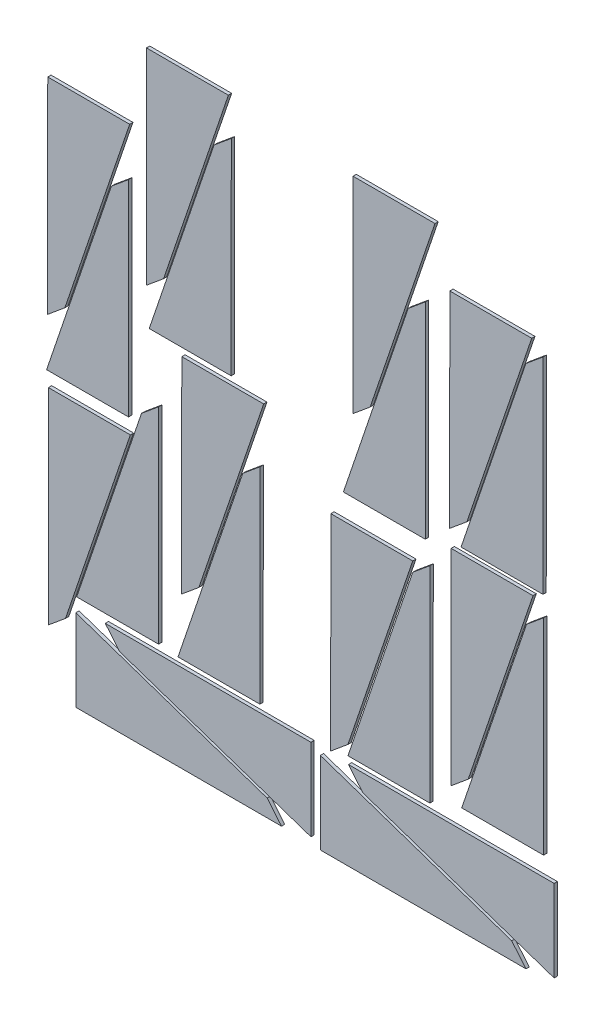
SolidWorks part; units mm, degrees
ref_plane "Front Plane" through (0, 0, 0) normal (0, 0, 1) x (1, 0, 0)
ref_plane "Top Plane" through (0, 0, 0) normal (0, 1, 0) x (1, 0, 0)
ref_plane "Right Plane" through (0, 0, 0) normal (1, 0, 0) x (0, 0, -1)
sketch "Model" plane through (0, 0, 0) normal (0, 0, 1) x (1, 0, 0)
  line L0 (81.73, 0) -> (81.73, 95)
  line L1 (77.73, 99) -> (4, 99)
  line L2 (0, 95) -> (0, 0)
  line L3 (0, 0) -> (9.25, 0)
  line L4 (10.55, -1.3) -> (10.55, -3)
  line L5 (10.55, -3) -> (34.415, -3)
  line L6 (47.315, -3) -> (71.18, -3)
  line L7 (71.18, -3) -> (71.18, -1.3)
  line L8 (72.48, 0) -> (81.73, 0)
  line L9 (35.715, 0) -> (46.015, 0)
  line L10 (34.415, -1.3) -> (34.415, -3)
  line L11 (47.315, -1.3) -> (47.315, -3)
  line L12 (0, 4) -> (9, 4)
  line L13 (9, 4) -> (9, 0)
  line L14 (81.73, 4) -> (72.73, 4)
  line L15 (72.73, 4) -> (72.73, 0)
  line L16 (34.4, 71.8) -> (32.6, 71.8)
  line L17 (32.6, 71.8) -> (32.6, 69)
  line L18 (32.6, 69) -> (34.4, 69)
  line L19 (34.4, 69) -> (34.4, 71.8)
  line L20 (32.5, 71.6) -> (32.5, 71.2)
  line L21 (32.5, 71.2) -> (32.4, 71.2)
  line L22 (32.4, 71.2) -> (32.4, 71.6)
  line L23 (32.4, 71.6) -> (32.5, 71.6)
  line L24 (14.7, 87.6) -> (14.7, 89.4)
  line L25 (14.7, 89.4) -> (11.9, 89.4)
  line L26 (11.9, 89.4) -> (11.9, 87.6)
  line L27 (11.9, 87.6) -> (14.7, 87.6)
  line L28 (14.5, 89.5) -> (14.1, 89.5)
  line L29 (14.1, 89.5) -> (14.1, 89.6)
  line L30 (14.1, 89.6) -> (14.5, 89.6)
  line L31 (14.5, 89.6) -> (14.5, 89.5)
  line L32 (20.8, 48.7) -> (22.6, 48.7)
  line L33 (22.6, 48.7) -> (22.6, 51.5)
  line L34 (22.6, 51.5) -> (20.8, 51.5)
  line L35 (20.8, 51.5) -> (20.8, 48.7)
  line L36 (22.7, 48.9) -> (22.7, 49.3)
  line L37 (22.7, 49.3) -> (22.8, 49.3)
  line L38 (22.8, 49.3) -> (22.8, 48.9)
  line L39 (22.8, 48.9) -> (22.7, 48.9)
  line L40 (5.4, 10.5) -> (3.6, 10.5)
  line L41 (3.6, 10.5) -> (3.6, 7.7)
  line L42 (3.6, 7.7) -> (5.4, 7.7)
  line L43 (5.4, 7.7) -> (5.4, 10.5)
  line L44 (3.5, 10.3) -> (3.5, 9.9)
  line L45 (3.5, 9.9) -> (3.4, 9.9)
  line L46 (3.4, 9.9) -> (3.4, 10.3)
  line L47 (3.4, 10.3) -> (3.5, 10.3)
  line L48 (20.1, 1.8) -> (20.1, 3.6)
  line L49 (20.1, 3.6) -> (17.3, 3.6)
  line L50 (17.3, 3.6) -> (17.3, 1.8)
  line L51 (17.3, 1.8) -> (20.1, 1.8)
  line L52 (19.9, 3.7) -> (19.5, 3.7)
  line L53 (19.5, 3.7) -> (19.5, 3.8)
  line L54 (19.5, 3.8) -> (19.9, 3.8)
  line L55 (19.9, 3.8) -> (19.9, 3.7)
  line L56 (65.5, 94.7) -> (63.7, 94.7)
  line L57 (63.7, 94.7) -> (63.7, 91.9)
  line L58 (63.7, 91.9) -> (65.5, 91.9)
  line L59 (65.5, 91.9) -> (65.5, 94.7)
  line L60 (63.6, 94.5) -> (63.6, 94.1)
  line L61 (63.6, 94.1) -> (63.5, 94.1)
  line L62 (63.5, 94.1) -> (63.5, 94.5)
  line L63 (63.5, 94.5) -> (63.6, 94.5)
  line L64 (61.8, 77.4) -> (63.6, 77.4)
  line L65 (63.6, 77.4) -> (63.6, 80.2)
  line L66 (63.6, 80.2) -> (61.8, 80.2)
  line L67 (61.8, 80.2) -> (61.8, 77.4)
  line L68 (63.7, 77.6) -> (63.7, 78)
  line L69 (63.7, 78) -> (63.8, 78)
  line L70 (63.8, 78) -> (63.8, 77.6)
  line L71 (63.8, 77.6) -> (63.7, 77.6)
  line L72 (62.1, 44.3) -> (63.9, 44.3)
  line L73 (63.9, 44.3) -> (63.9, 47.1)
  line L74 (63.9, 47.1) -> (62.1, 47.1)
  line L75 (62.1, 47.1) -> (62.1, 44.3)
  line L76 (64, 44.5) -> (64, 44.9)
  line L77 (64, 44.9) -> (64.1, 44.9)
  line L78 (64.1, 44.9) -> (64.1, 44.5)
  line L79 (64.1, 44.5) -> (64, 44.5)
  line L80 (43.3, 37.5) -> (45.1, 37.5)
  line L81 (45.1, 37.5) -> (45.1, 40.3)
  line L82 (45.1, 40.3) -> (43.3, 40.3)
  line L83 (43.3, 40.3) -> (43.3, 37.5)
  line L84 (45.2, 37.7) -> (45.2, 38.1)
  line L85 (45.2, 38.1) -> (45.3, 38.1)
  line L86 (45.3, 38.1) -> (45.3, 37.7)
  line L87 (45.3, 37.7) -> (45.2, 37.7)
  line L88 (57.3, 2) -> (57.3, 3.8)
  line L89 (57.3, 3.8) -> (54.5, 3.8)
  line L90 (54.5, 3.8) -> (54.5, 2)
  line L91 (54.5, 2) -> (57.3, 2)
  line L92 (57.1, 3.9) -> (56.7, 3.9)
  line L93 (56.7, 3.9) -> (56.7, 4)
  line L94 (56.7, 4) -> (57.1, 4)
  line L95 (57.1, 4) -> (57.1, 3.9)
  line L96 (38.3, 58.7) -> (40.1, 58.7)
  line L97 (40.1, 58.7) -> (40.1, 61.5)
  line L98 (40.1, 61.5) -> (38.3, 61.5)
  line L99 (38.3, 61.5) -> (38.3, 58.7)
  line L100 (40.2, 58.9) -> (40.2, 59.3)
  line L101 (40.2, 59.3) -> (40.3, 59.3)
  line L102 (40.3, 59.3) -> (40.3, 58.9)
  line L103 (40.3, 58.9) -> (40.2, 58.9)
  line L104 (41.8, 58.7) -> (43.6, 58.7)
  line L105 (43.6, 58.7) -> (43.6, 61.5)
  line L106 (43.6, 61.5) -> (41.8, 61.5)
  line L107 (41.8, 61.5) -> (41.8, 58.7)
  line L108 (43.7, 58.9) -> (43.7, 59.3)
  line L109 (43.7, 59.3) -> (43.8, 59.3)
  line L110 (43.8, 59.3) -> (43.8, 58.9)
  line L111 (43.8, 58.9) -> (43.7, 58.9)
  line L112 (18.0727, 97.8187) -> (18.0543, 66.371)
  line L113 (18.0543, 66.371) -> (20.6886, 68.5619)
  line L114 (20.6886, 68.5619) -> (30.6039, 97.834)
  line L115 (30.6039, 97.834) -> (18.0811, 97.8343)
  line L116 (16.3763, 95.3169) -> (17.1559, 95.3169)
  line L117 (31.0273, 60.8813) -> (31.0457, 92.329)
  line L118 (31.0457, 92.329) -> (28.4114, 90.1381)
  line L119 (28.4114, 90.1381) -> (18.4961, 60.866)
  line L120 (18.4961, 60.866) -> (31.0189, 60.8657)
  line L121 (31.6559, 63.3841) -> (32.4355, 63.3841)
  line L122 (2.9727, 86.4187) -> (2.9543, 54.971)
  line L123 (2.9543, 54.971) -> (5.5886, 57.1619)
  line L124 (5.5886, 57.1619) -> (15.5039, 86.434)
  line L125 (15.5039, 86.434) -> (2.9811, 86.4343)
  line L126 (1.2763, 83.9169) -> (2.0559, 83.9169)
  line L127 (15.3273, 47.5813) -> (15.3457, 79.029)
  line L128 (15.3457, 79.029) -> (12.7114, 76.8381)
  line L129 (12.7114, 76.8381) -> (2.7961, 47.566)
  line L130 (2.7961, 47.566) -> (15.3189, 47.5657)
  line L131 (15.9559, 50.0841) -> (16.7355, 50.0841)
  line L132 (23.4727, 59.6187) -> (23.4543, 28.171)
  line L133 (23.4543, 28.171) -> (26.0886, 30.3619)
  line L134 (26.0886, 30.3619) -> (36.0039, 59.634)
  line L135 (36.0039, 59.634) -> (23.4811, 59.6343)
  line L136 (21.7763, 57.1169) -> (22.5559, 57.1169)
  line L137 (35.4273, 19.5813) -> (35.4457, 51.029)
  line L138 (35.4457, 51.029) -> (32.8114, 48.8381)
  line L139 (32.8114, 48.8381) -> (22.8961, 19.566)
  line L140 (22.8961, 19.566) -> (35.4189, 19.5657)
  line L141 (36.0559, 22.0841) -> (36.8355, 22.0841)
  line L142 (19.9273, 19.7813) -> (19.9457, 51.229)
  line L143 (19.9457, 51.229) -> (17.3114, 49.0381)
  line L144 (17.3114, 49.0381) -> (7.3961, 19.766)
  line L145 (7.3961, 19.766) -> (19.9189, 19.7657)
  line L146 (20.5559, 22.2841) -> (21.3355, 22.2841)
  line L147 (3.0727, 45.3187) -> (3.0543, 13.871)
  line L148 (3.0543, 13.871) -> (5.6886, 16.0619)
  line L149 (5.6886, 16.0619) -> (15.6039, 45.334)
  line L150 (15.6039, 45.334) -> (3.0811, 45.3343)
  line L151 (1.3763, 42.8169) -> (2.1559, 42.8169)
  line L152 (43.2187, 18.4273) -> (11.771, 18.4457)
  line L153 (11.771, 18.4457) -> (13.9619, 15.8114)
  line L154 (13.9619, 15.8114) -> (43.234, 5.8961)
  line L155 (43.234, 5.8961) -> (43.2343, 18.4189)
  line L156 (40.7159, 19.0559) -> (40.7159, 19.8355)
  line L157 (7.2813, 5.0727) -> (38.729, 5.0543)
  line L158 (38.729, 5.0543) -> (36.5381, 7.6886)
  line L159 (36.5381, 7.6886) -> (7.266, 17.6039)
  line L160 (7.266, 17.6039) -> (7.2657, 5.0811)
  line L161 (9.7831, 3.3763) -> (9.7831, 4.1559)
  line L162 (49.6727, 96.6187) -> (49.6543, 65.171)
  line L163 (49.6543, 65.171) -> (52.2886, 67.3619)
  line L164 (52.2886, 67.3619) -> (62.2039, 96.634)
  line L165 (62.2039, 96.634) -> (49.6811, 96.6343)
  line L166 (47.9763, 94.1169) -> (48.7559, 94.1169)
  line L167 (60.7273, 54.0813) -> (60.7457, 85.529)
  line L168 (60.7457, 85.529) -> (58.1114, 83.3381)
  line L169 (58.1114, 83.3381) -> (48.1961, 54.066)
  line L170 (48.1961, 54.066) -> (60.7189, 54.0657)
  line L171 (61.3559, 56.5841) -> (62.1355, 56.5841)
  line L172 (64.4727, 88.8187) -> (64.4543, 57.371)
  line L173 (64.4543, 57.371) -> (67.0886, 59.5619)
  line L174 (67.0886, 59.5619) -> (77.0039, 88.834)
  line L175 (77.0039, 88.834) -> (64.4811, 88.8343)
  line L176 (62.7763, 86.3169) -> (63.5559, 86.3169)
  line L177 (78.7273, 55.7813) -> (78.7457, 87.229)
  line L178 (78.7457, 87.229) -> (76.1114, 85.0381)
  line L179 (76.1114, 85.0381) -> (66.1961, 55.766)
  line L180 (66.1961, 55.766) -> (78.7189, 55.7657)
  line L181 (79.3559, 58.2841) -> (80.1355, 58.2841)
  line L182 (64.6727, 54.8187) -> (64.6543, 23.371)
  line L183 (64.6543, 23.371) -> (67.2886, 25.5619)
  line L184 (67.2886, 25.5619) -> (77.2039, 54.834)
  line L185 (77.2039, 54.834) -> (64.6811, 54.8343)
  line L186 (62.9763, 52.3169) -> (63.7559, 52.3169)
  line L187 (78.8273, 21.2813) -> (78.8457, 52.729)
  line L188 (78.8457, 52.729) -> (76.2114, 50.5381)
  line L189 (76.2114, 50.5381) -> (66.2961, 21.266)
  line L190 (66.2961, 21.266) -> (78.8189, 21.2657)
  line L191 (79.4559, 23.7841) -> (80.2355, 23.7841)
  line L192 (61.4273, 19.4813) -> (61.4457, 50.929)
  line L193 (61.4457, 50.929) -> (58.8114, 48.7381)
  line L194 (58.8114, 48.7381) -> (48.8961, 19.466)
  line L195 (48.8961, 19.466) -> (61.4189, 19.4657)
  line L196 (62.0559, 21.9841) -> (62.8355, 21.9841)
  line L197 (46.2727, 50.2187) -> (46.2543, 18.771)
  line L198 (46.2543, 18.771) -> (48.8886, 20.9619)
  line L199 (48.8886, 20.9619) -> (58.8039, 50.234)
  line L200 (58.8039, 50.234) -> (46.2811, 50.2343)
  line L201 (44.5763, 47.7169) -> (45.3559, 47.7169)
  line L202 (80.4187, 18.3273) -> (48.971, 18.3457)
  line L203 (48.971, 18.3457) -> (51.1619, 15.7114)
  line L204 (51.1619, 15.7114) -> (80.434, 5.7961)
  line L205 (80.434, 5.7961) -> (80.4343, 18.3189)
  line L206 (77.9159, 18.9559) -> (77.9159, 19.7355)
  line L207 (44.6813, 4.8727) -> (76.129, 4.8543)
  line L208 (76.129, 4.8543) -> (73.9381, 7.4886)
  line L209 (73.9381, 7.4886) -> (44.666, 17.4039)
  line L210 (44.666, 17.4039) -> (44.6657, 4.8811)
  line L211 (47.1831, 3.1763) -> (47.1831, 3.9559)
  line L212 (2.9727, 86.4187) -> (2.9727, 86.4343)
  line L213 (2.9727, 86.4343) -> (2.9811, 86.4343)
  line L214 (15.3273, 47.5813) -> (15.3273, 47.5657)
  line L215 (15.3273, 47.5657) -> (15.3189, 47.5657)
  line L216 (18.0727, 97.8187) -> (18.0727, 97.8343)
  line L217 (18.0727, 97.8343) -> (18.0811, 97.8343)
  line L218 (31.0273, 60.8813) -> (31.0273, 60.8657)
  line L219 (31.0273, 60.8657) -> (31.0189, 60.8657)
  line L220 (23.4727, 59.6187) -> (23.4727, 59.6343)
  line L221 (23.4727, 59.6343) -> (23.4811, 59.6343)
  line L222 (35.4273, 19.5813) -> (35.4273, 19.5657)
  line L223 (35.4273, 19.5657) -> (35.4189, 19.5657)
  line L224 (3.0727, 45.3187) -> (3.0727, 45.3343)
  line L225 (3.0727, 45.3343) -> (3.0811, 45.3343)
  line L226 (19.9273, 19.7813) -> (19.9273, 19.7654)
  line L227 (19.9273, 19.7654) -> (19.9189, 19.7657)
  line L228 (7.2657, 5.0811) -> (7.2657, 5.0727)
  line L229 (7.2657, 5.0727) -> (7.2813, 5.0727)
  line L230 (43.2187, 18.4273) -> (43.2343, 18.4273)
  line L231 (43.2343, 18.4273) -> (43.2343, 18.4189)
  line L232 (43.2343, 18.4189) -> (43.2344, 18.4188)
  line L233 (44.6657, 4.8811) -> (44.6657, 4.8727)
  line L234 (44.6657, 4.8727) -> (44.6813, 4.8727)
  line L235 (44.6813, 4.8727) -> (44.6811, 4.8729)
  line L236 (80.4187, 18.3273) -> (80.4343, 18.3273)
  line L237 (80.4343, 18.3273) -> (80.4343, 18.3189)
  line L238 (78.8273, 21.2813) -> (78.8273, 21.2657)
  line L239 (78.8273, 21.2657) -> (78.8189, 21.2657)
  line L240 (64.6727, 54.8187) -> (64.6727, 54.8343)
  line L241 (64.6727, 54.8343) -> (64.6811, 54.8343)
  line L242 (64.6811, 54.8343) -> (64.6808, 54.8344)
  line L243 (61.4273, 19.4813) -> (61.4273, 19.4657)
  line L244 (61.4273, 19.4657) -> (61.4189, 19.4657)
  line L245 (46.2727, 50.2187) -> (46.2727, 50.2343)
  line L246 (46.2727, 50.2343) -> (46.2811, 50.2343)
  line L247 (60.7273, 54.0813) -> (60.7273, 54.0657)
  line L248 (60.7273, 54.0657) -> (60.7189, 54.0657)
  line L249 (49.6727, 96.6187) -> (49.6727, 96.6343)
  line L250 (49.6727, 96.6343) -> (49.6811, 96.6343)
  line L251 (64.4727, 88.8187) -> (64.4727, 88.8343)
  line L252 (64.4727, 88.8343) -> (64.4811, 88.8343)
  line L253 (78.7273, 55.7813) -> (78.7273, 55.7657)
  line L254 (78.7273, 55.7657) -> (78.7189, 55.7657)
  arc A0 (81.73, 95) -> (77.73, 99) centre (77.73, 95) ccw
  arc A1 (4, 99) -> (0, 95) centre (4, 95) ccw
  arc A2 (10.55, -1.3) -> (9.25, 0) centre (9.25, -1.3) ccw
  arc A3 (35.715, 0) -> (34.415, -1.3) centre (35.715, -1.3) ccw
  arc A4 (47.315, -1.3) -> (46.015, 0) centre (46.015, -1.3) ccw
  arc A5 (72.48, 0) -> (71.18, -1.3) centre (72.48, -1.3) ccw
  circle A6 centre (5, 94) radius 1.6
  circle A7 centre (76.73, 94) radius 1.6
  arc A8 (9, 3.8984) -> (9, 4.1016) centre (9, 4) ccw
  arc A9 (0, 4.1016) -> (0, 3.8984) centre (0, 4) ccw
  arc A10 (8.8984, 0) -> (9.1016, 0) centre (9, 0) ccw
  arc A11 (9.1016, 4) -> (8.8984, 4) centre (9, 4) ccw
  arc A12 (72.73, 4.1016) -> (72.73, 3.8984) centre (72.73, 4) ccw
  arc A13 (81.73, 3.8984) -> (81.73, 4.1016) centre (81.73, 4) ccw
  arc A14 (72.6284, 0) -> (72.8316, 0) centre (72.73, 0) ccw
  arc A15 (72.8316, 4) -> (72.6284, 4) centre (72.73, 4) ccw
  circle A16 centre (5, 94) radius 3
  circle A17 centre (76.73, 94) radius 3
  arc A18 (32.6, 71.8317) -> (32.6, 71.7682) centre (32.6, 71.7999) ccw
  arc A19 (34.4, 71.7682) -> (34.4, 71.8317) centre (34.4, 71.7999) ccw
  arc A20 (32.5682, 69) -> (32.6318, 69) centre (32.6, 69) ccw
  arc A21 (32.6318, 71.8) -> (32.5682, 71.8) centre (32.6, 71.8) ccw
  arc A22 (34.4, 68.9682) -> (34.4, 69.0318) centre (34.4, 69) ccw
  arc A23 (32.6, 69.0318) -> (32.6, 68.9682) centre (32.6, 69) ccw
  arc A24 (34.4318, 71.8) -> (34.3682, 71.8) centre (34.4, 71.8) ccw
  arc A25 (34.3682, 69) -> (34.4318, 69) centre (34.4, 69) ccw
  arc A26 (32.4682, 71.2) -> (32.5318, 71.2) centre (32.5, 71.2) ccw
  arc A27 (32.5318, 71.6) -> (32.4682, 71.6) centre (32.5, 71.6) ccw
  arc A28 (32.4, 71.2318) -> (32.4, 71.1683) centre (32.4, 71.2001) ccw
  arc A29 (32.5, 71.1683) -> (32.5, 71.2318) centre (32.5, 71.2001) ccw
  arc A30 (32.4318, 71.6) -> (32.3682, 71.6) centre (32.4, 71.6) ccw
  arc A31 (32.3682, 71.2) -> (32.4318, 71.2) centre (32.4, 71.2) ccw
  arc A32 (32.5, 71.5683) -> (32.5, 71.6318) centre (32.5, 71.6) ccw
  arc A33 (32.4, 71.6318) -> (32.4, 71.5683) centre (32.4, 71.6) ccw
  arc A34 (14.7318, 89.4) -> (14.6683, 89.4) centre (14.7, 89.4) ccw
  arc A35 (14.6683, 87.6) -> (14.7318, 87.6) centre (14.7, 87.6) ccw
  arc A36 (11.9, 89.4318) -> (11.9, 89.3683) centre (11.9, 89.4001) ccw
  arc A37 (14.7, 89.3683) -> (14.7, 89.4318) centre (14.7, 89.4001) ccw
  arc A38 (11.8682, 87.6) -> (11.9318, 87.6) centre (11.9, 87.6) ccw
  arc A39 (11.9318, 89.4) -> (11.8682, 89.4) centre (11.9, 89.4) ccw
  arc A40 (14.7, 87.5683) -> (14.7, 87.6318) centre (14.7, 87.6) ccw
  arc A41 (11.9, 87.6318) -> (11.9, 87.5683) centre (11.9, 87.6) ccw
  arc A42 (14.1, 89.5318) -> (14.1, 89.4682) centre (14.1, 89.5) ccw
  arc A43 (14.5, 89.4682) -> (14.5, 89.5318) centre (14.5, 89.5) ccw
  arc A44 (14.1318, 89.6) -> (14.0683, 89.6) centre (14.1, 89.6) ccw
  arc A45 (14.0683, 89.5) -> (14.1318, 89.5) centre (14.1, 89.5) ccw
  arc A46 (14.5, 89.5683) -> (14.5, 89.6318) centre (14.5, 89.6) ccw
  arc A47 (14.1, 89.6318) -> (14.1, 89.5683) centre (14.1, 89.6) ccw
  arc A48 (14.4682, 89.5) -> (14.5318, 89.5) centre (14.5, 89.5) ccw
  arc A49 (14.5318, 89.6) -> (14.4682, 89.6) centre (14.5, 89.6) ccw
  arc A50 (22.6, 48.6683) -> (22.6, 48.7318) centre (22.6, 48.7001) ccw
  arc A51 (20.8, 48.7318) -> (20.8, 48.6683) centre (20.8, 48.7001) ccw
  arc A52 (22.6318, 51.5) -> (22.5683, 51.5) centre (22.6, 51.5) ccw
  arc A53 (22.5683, 48.7) -> (22.6318, 48.7) centre (22.6, 48.7) ccw
  arc A54 (20.8, 51.5318) -> (20.8, 51.4682) centre (20.8, 51.5) ccw
  arc A55 (22.6, 51.4682) -> (22.6, 51.5318) centre (22.6, 51.5) ccw
  arc A56 (20.7683, 48.7) -> (20.8317, 48.7) centre (20.8, 48.7) ccw
  arc A57 (20.8317, 51.5) -> (20.7683, 51.5) centre (20.8, 51.5) ccw
  arc A58 (22.7318, 49.3) -> (22.6683, 49.3) centre (22.7001, 49.3) ccw
  arc A59 (22.6683, 48.9) -> (22.7318, 48.9) centre (22.7001, 48.9) ccw
  arc A60 (22.8, 49.2683) -> (22.8, 49.3318) centre (22.8, 49.3001) ccw
  arc A61 (22.7, 49.3318) -> (22.7, 49.2683) centre (22.7, 49.3001) ccw
  arc A62 (22.7683, 48.9) -> (22.8317, 48.9) centre (22.8, 48.9) ccw
  arc A63 (22.8317, 49.3) -> (22.7683, 49.3) centre (22.8, 49.3) ccw
  arc A64 (22.7, 48.9318) -> (22.7, 48.8683) centre (22.7, 48.9001) ccw
  arc A65 (22.8, 48.8683) -> (22.8, 48.9318) centre (22.8, 48.9001) ccw
  arc A66 (3.6, 10.5318) -> (3.6, 10.4682) centre (3.6, 10.5) ccw
  arc A67 (5.4, 10.4682) -> (5.4, 10.5318) centre (5.4, 10.5) ccw
  arc A68 (3.5682, 7.7) -> (3.6318, 7.7) centre (3.6, 7.7) ccw
  arc A69 (3.6318, 10.5) -> (3.5682, 10.5) centre (3.6, 10.5) ccw
  arc A70 (5.4, 7.6683) -> (5.4, 7.7317) centre (5.4, 7.7) ccw
  arc A71 (3.6, 7.7317) -> (3.6, 7.6683) centre (3.6, 7.7) ccw
  arc A72 (5.4318, 10.5) -> (5.3683, 10.5) centre (5.4001, 10.5) ccw
  arc A73 (5.3683, 7.7) -> (5.4318, 7.7) centre (5.4001, 7.7) ccw
  arc A74 (3.4682, 9.9) -> (3.5318, 9.9) centre (3.5, 9.9) ccw
  arc A75 (3.5318, 10.3) -> (3.4682, 10.3) centre (3.5, 10.3) ccw
  arc A76 (3.4, 9.9318) -> (3.4, 9.8682) centre (3.4, 9.9) ccw
  arc A77 (3.5, 9.8682) -> (3.5, 9.9318) centre (3.5, 9.9) ccw
  arc A78 (3.4318, 10.3) -> (3.3683, 10.3) centre (3.4, 10.3) ccw
  arc A79 (3.3683, 9.9) -> (3.4318, 9.9) centre (3.4, 9.9) ccw
  arc A80 (3.5, 10.2683) -> (3.5, 10.3318) centre (3.5, 10.3001) ccw
  arc A81 (3.4, 10.3318) -> (3.4, 10.2683) centre (3.4, 10.3001) ccw
  arc A82 (20.1318, 3.6) -> (20.0683, 3.6) centre (20.1, 3.6) ccw
  arc A83 (20.0683, 1.8) -> (20.1318, 1.8) centre (20.1, 1.8) ccw
  arc A84 (17.3, 3.6318) -> (17.3, 3.5682) centre (17.3, 3.6) ccw
  arc A85 (20.1, 3.5682) -> (20.1, 3.6318) centre (20.1, 3.6) ccw
  arc A86 (17.2683, 1.8) -> (17.3317, 1.8) centre (17.3, 1.8) ccw
  arc A87 (17.3317, 3.6) -> (17.2683, 3.6) centre (17.3, 3.6) ccw
  arc A88 (20.1, 1.7683) -> (20.1, 1.8317) centre (20.1, 1.8) ccw
  arc A89 (17.3, 1.8317) -> (17.3, 1.7683) centre (17.3, 1.8) ccw
  arc A90 (19.5, 3.7318) -> (19.5, 3.6683) centre (19.5, 3.7001) ccw
  arc A91 (19.9, 3.6683) -> (19.9, 3.7318) centre (19.9, 3.7001) ccw
  arc A92 (19.5317, 3.8) -> (19.4683, 3.8) centre (19.5, 3.8) ccw
  arc A93 (19.4683, 3.7) -> (19.5317, 3.7) centre (19.5, 3.7) ccw
  arc A94 (19.9, 3.7683) -> (19.9, 3.8318) centre (19.9, 3.8001) ccw
  arc A95 (19.5, 3.8318) -> (19.5, 3.7683) centre (19.5, 3.8001) ccw
  arc A96 (19.8683, 3.7) -> (19.9318, 3.7) centre (19.9001, 3.7) ccw
  arc A97 (19.9318, 3.8) -> (19.8683, 3.8) centre (19.9001, 3.8) ccw
  arc A98 (63.7, 94.7318) -> (63.7, 94.6683) centre (63.7, 94.7001) ccw
  arc A99 (65.5, 94.6683) -> (65.5, 94.7318) centre (65.5, 94.7001) ccw
  arc A100 (63.6683, 91.9) -> (63.7318, 91.9) centre (63.7001, 91.9) ccw
  arc A101 (63.7318, 94.7) -> (63.6683, 94.7) centre (63.7001, 94.7) ccw
  arc A102 (65.5, 91.8683) -> (65.5, 91.9318) centre (65.5, 91.9) ccw
  arc A103 (63.7, 91.9318) -> (63.7, 91.8683) centre (63.7, 91.9) ccw
  arc A104 (65.5318, 94.7) -> (65.4682, 94.7) centre (65.5, 94.7) ccw
  arc A105 (65.4682, 91.9) -> (65.5318, 91.9) centre (65.5, 91.9) ccw
  arc A106 (63.5682, 94.1) -> (63.6318, 94.1) centre (63.6, 94.1) ccw
  arc A107 (63.6318, 94.5) -> (63.5682, 94.5) centre (63.6, 94.5) ccw
  arc A108 (63.5, 94.1318) -> (63.5, 94.0683) centre (63.5, 94.1) ccw
  arc A109 (63.6, 94.0683) -> (63.6, 94.1318) centre (63.6, 94.1) ccw
  arc A110 (63.5318, 94.5) -> (63.4682, 94.5) centre (63.5, 94.5) ccw
  arc A111 (63.4682, 94.1) -> (63.5318, 94.1) centre (63.5, 94.1) ccw
  arc A112 (63.6, 94.4682) -> (63.6, 94.5318) centre (63.6, 94.5) ccw
  arc A113 (63.5, 94.5318) -> (63.5, 94.4682) centre (63.5, 94.5) ccw
  arc A114 (63.6, 77.3683) -> (63.6, 77.4318) centre (63.6, 77.4) ccw
  arc A115 (61.8, 77.4318) -> (61.8, 77.3683) centre (61.8, 77.4) ccw
  arc A116 (63.6318, 80.2) -> (63.5682, 80.2) centre (63.6, 80.2) ccw
  arc A117 (63.5682, 77.4) -> (63.6318, 77.4) centre (63.6, 77.4) ccw
  arc A118 (61.8, 80.2318) -> (61.8, 80.1683) centre (61.8, 80.2) ccw
  arc A119 (63.6, 80.1683) -> (63.6, 80.2318) centre (63.6, 80.2) ccw
  arc A120 (61.7683, 77.4) -> (61.8318, 77.4) centre (61.8, 77.4) ccw
  arc A121 (61.8318, 80.2) -> (61.7683, 80.2) centre (61.8, 80.2) ccw
  arc A122 (63.7318, 78) -> (63.6683, 78) centre (63.7001, 78) ccw
  arc A123 (63.6683, 77.6) -> (63.7318, 77.6) centre (63.7001, 77.6) ccw
  arc A124 (63.8, 77.9682) -> (63.8, 78.0318) centre (63.8, 78) ccw
  arc A125 (63.7, 78.0318) -> (63.7, 77.9682) centre (63.7, 78) ccw
  arc A126 (63.7683, 77.6) -> (63.8318, 77.6) centre (63.8, 77.6) ccw
  arc A127 (63.8318, 78) -> (63.7683, 78) centre (63.8, 78) ccw
  arc A128 (63.7, 77.6318) -> (63.7, 77.5683) centre (63.7, 77.6001) ccw
  arc A129 (63.8, 77.5683) -> (63.8, 77.6318) centre (63.8, 77.6001) ccw
  arc A130 (63.9, 44.2683) -> (63.9, 44.3318) centre (63.9, 44.3001) ccw
  arc A131 (62.1, 44.3318) -> (62.1, 44.2683) centre (62.1, 44.3001) ccw
  arc A132 (63.9318, 47.1) -> (63.8683, 47.1) centre (63.9001, 47.1) ccw
  arc A133 (63.8683, 44.3) -> (63.9318, 44.3) centre (63.9001, 44.3) ccw
  arc A134 (62.1, 47.1318) -> (62.1, 47.0682) centre (62.1, 47.1) ccw
  arc A135 (63.9, 47.0682) -> (63.9, 47.1318) centre (63.9, 47.1) ccw
  arc A136 (62.0682, 44.3) -> (62.1318, 44.3) centre (62.1, 44.3) ccw
  arc A137 (62.1318, 47.1) -> (62.0682, 47.1) centre (62.1, 47.1) ccw
  arc A138 (64.0318, 44.9) -> (63.9682, 44.9) centre (64, 44.9) ccw
  arc A139 (63.9682, 44.5) -> (64.0318, 44.5) centre (64, 44.5) ccw
  arc A140 (64.1, 44.8683) -> (64.1, 44.9318) centre (64.1, 44.9001) ccw
  arc A141 (64, 44.9318) -> (64, 44.8683) centre (64, 44.9001) ccw
  arc A142 (64.0683, 44.5) -> (64.1318, 44.5) centre (64.1, 44.5) ccw
  arc A143 (64.1318, 44.9) -> (64.0683, 44.9) centre (64.1, 44.9) ccw
  arc A144 (64, 44.5318) -> (64, 44.4682) centre (64, 44.5) ccw
  arc A145 (64.1, 44.4682) -> (64.1, 44.5318) centre (64.1, 44.5) ccw
  arc A146 (45.1, 37.4682) -> (45.1, 37.5318) centre (45.1, 37.5) ccw
  arc A147 (43.3, 37.5318) -> (43.3, 37.4682) centre (43.3, 37.5) ccw
  arc A148 (45.1318, 40.3) -> (45.0682, 40.3) centre (45.1, 40.3) ccw
  arc A149 (45.0682, 37.5) -> (45.1318, 37.5) centre (45.1, 37.5) ccw
  arc A150 (43.3, 40.3318) -> (43.3, 40.2683) centre (43.3, 40.3001) ccw
  arc A151 (45.1, 40.2683) -> (45.1, 40.3318) centre (45.1, 40.3001) ccw
  arc A152 (43.2683, 37.5) -> (43.3318, 37.5) centre (43.3001, 37.5) ccw
  arc A153 (43.3318, 40.3) -> (43.2683, 40.3) centre (43.3001, 40.3) ccw
  arc A154 (45.2318, 38.1) -> (45.1683, 38.1) centre (45.2001, 38.1) ccw
  arc A155 (45.1683, 37.7) -> (45.2318, 37.7) centre (45.2001, 37.7) ccw
  arc A156 (45.3, 38.0682) -> (45.3, 38.1318) centre (45.3, 38.1) ccw
  arc A157 (45.2, 38.1318) -> (45.2, 38.0682) centre (45.2, 38.1) ccw
  arc A158 (45.2683, 37.7) -> (45.3318, 37.7) centre (45.3001, 37.7) ccw
  arc A159 (45.3318, 38.1) -> (45.2683, 38.1) centre (45.3001, 38.1) ccw
  arc A160 (45.2, 37.7318) -> (45.2, 37.6683) centre (45.2, 37.7) ccw
  arc A161 (45.3, 37.6683) -> (45.3, 37.7318) centre (45.3, 37.7) ccw
  arc A162 (57.3318, 3.8) -> (57.2683, 3.8) centre (57.3001, 3.8) ccw
  arc A163 (57.2683, 2) -> (57.3318, 2) centre (57.3001, 2) ccw
  arc A164 (54.5, 3.8318) -> (54.5, 3.7683) centre (54.5, 3.8001) ccw
  arc A165 (57.3, 3.7683) -> (57.3, 3.8318) centre (57.3, 3.8001) ccw
  arc A166 (54.4682, 2) -> (54.5318, 2) centre (54.5, 2) ccw
  arc A167 (54.5318, 3.8) -> (54.4682, 3.8) centre (54.5, 3.8) ccw
  arc A168 (57.3, 1.9683) -> (57.3, 2.0318) centre (57.3, 2.0001) ccw
  arc A169 (54.5, 2.0318) -> (54.5, 1.9683) centre (54.5, 2.0001) ccw
  arc A170 (56.7, 3.9318) -> (56.7, 3.8683) centre (56.7, 3.9001) ccw
  arc A171 (57.1, 3.8683) -> (57.1, 3.9318) centre (57.1, 3.9001) ccw
  arc A172 (56.7318, 4) -> (56.6683, 4) centre (56.7001, 4) ccw
  arc A173 (56.6683, 3.9) -> (56.7318, 3.9) centre (56.7001, 3.9) ccw
  arc A174 (57.1, 3.9682) -> (57.1, 4.0317) centre (57.1, 4) ccw
  arc A175 (56.7, 4.0317) -> (56.7, 3.9682) centre (56.7, 4) ccw
  arc A176 (57.0682, 3.9) -> (57.1318, 3.9) centre (57.1, 3.9) ccw
  arc A177 (57.1318, 4) -> (57.0682, 4) centre (57.1, 4) ccw
  arc A178 (40.1, 58.6683) -> (40.1, 58.7318) centre (40.1, 58.7001) ccw
  arc A179 (38.3, 58.7318) -> (38.3, 58.6683) centre (38.3, 58.7001) ccw
  arc A180 (40.1318, 61.5) -> (40.0682, 61.5) centre (40.1, 61.5) ccw
  arc A181 (40.0682, 58.7) -> (40.1318, 58.7) centre (40.1, 58.7) ccw
  arc A182 (38.3, 61.5318) -> (38.3, 61.4682) centre (38.3, 61.5) ccw
  arc A183 (40.1, 61.4682) -> (40.1, 61.5318) centre (40.1, 61.5) ccw
  arc A184 (38.2683, 58.7) -> (38.3318, 58.7) centre (38.3, 58.7) ccw
  arc A185 (38.3318, 61.5) -> (38.2683, 61.5) centre (38.3, 61.5) ccw
  arc A186 (40.2318, 59.3) -> (40.1683, 59.3) centre (40.2001, 59.3) ccw
  arc A187 (40.1683, 58.9) -> (40.2318, 58.9) centre (40.2001, 58.9) ccw
  arc A188 (40.3, 59.2683) -> (40.3, 59.3318) centre (40.3, 59.3001) ccw
  arc A189 (40.2, 59.3318) -> (40.2, 59.2683) centre (40.2, 59.3001) ccw
  arc A190 (40.2683, 58.9) -> (40.3318, 58.9) centre (40.3001, 58.9) ccw
  arc A191 (40.3318, 59.3) -> (40.2683, 59.3) centre (40.3001, 59.3) ccw
  arc A192 (40.2, 58.9318) -> (40.2, 58.8683) centre (40.2, 58.9001) ccw
  arc A193 (40.3, 58.8683) -> (40.3, 58.9318) centre (40.3, 58.9001) ccw
  arc A194 (43.6, 58.6683) -> (43.6, 58.7318) centre (43.6, 58.7001) ccw
  arc A195 (41.8, 58.7318) -> (41.8, 58.6683) centre (41.8, 58.7001) ccw
  arc A196 (43.6318, 61.5) -> (43.5682, 61.5) centre (43.6, 61.5) ccw
  arc A197 (43.5682, 58.7) -> (43.6318, 58.7) centre (43.6, 58.7) ccw
  arc A198 (41.8, 61.5318) -> (41.8, 61.4682) centre (41.8, 61.5) ccw
  arc A199 (43.6, 61.4682) -> (43.6, 61.5318) centre (43.6, 61.5) ccw
  arc A200 (41.7683, 58.7) -> (41.8318, 58.7) centre (41.8001, 58.7) ccw
  arc A201 (41.8318, 61.5) -> (41.7683, 61.5) centre (41.8001, 61.5) ccw
  arc A202 (43.7318, 59.3) -> (43.6683, 59.3) centre (43.7001, 59.3) ccw
  arc A203 (43.6683, 58.9) -> (43.7318, 58.9) centre (43.7001, 58.9) ccw
  arc A204 (43.8, 59.2683) -> (43.8, 59.3318) centre (43.8, 59.3001) ccw
  arc A205 (43.7, 59.3318) -> (43.7, 59.2683) centre (43.7, 59.3001) ccw
  arc A206 (43.7683, 58.9) -> (43.8318, 58.9) centre (43.8001, 58.9) ccw
  arc A207 (43.8318, 59.3) -> (43.7683, 59.3) centre (43.8001, 59.3) ccw
  arc A208 (43.7, 58.9318) -> (43.7, 58.8683) centre (43.7, 58.9001) ccw
  arc A209 (43.8, 58.8683) -> (43.8, 58.9318) centre (43.8, 58.9001) ccw
  arc A210 (18.0226, 66.371) -> (18.086, 66.371) centre (18.0543, 66.371) ccw
  arc A211 (18.1044, 97.8187) -> (18.041, 97.8187) centre (18.0727, 97.8187) ccw
  arc A212 (20.7089, 68.5375) -> (20.6683, 68.5863) centre (20.6886, 68.5619) ccw
  arc A213 (18.034, 66.3954) -> (18.0746, 66.3466) centre (18.0543, 66.371) ccw
  arc A214 (30.634, 97.8238) -> (30.5738, 97.8442) centre (30.6039, 97.834) ccw
  arc A215 (20.6585, 68.5721) -> (20.7187, 68.5517) centre (20.6886, 68.5619) ccw
  arc A216 (18.0811, 97.866) -> (18.0811, 97.8026) centre (18.0811, 97.8343) ccw
  arc A217 (30.6039, 97.8023) -> (30.6039, 97.8657) centre (30.6039, 97.834) ccw
  arc A218 (17.1559, 95.2915) -> (17.1559, 95.3423) centre (17.1559, 95.3169) ccw
  arc A219 (16.3763, 95.3423) -> (16.3763, 95.2915) centre (16.3763, 95.3169) ccw
  arc A220 (31.0774, 92.329) -> (31.014, 92.329) centre (31.0457, 92.329) ccw
  arc A221 (30.9956, 60.8813) -> (31.059, 60.8813) centre (31.0273, 60.8813) ccw
  arc A222 (28.3911, 90.1625) -> (28.4317, 90.1137) centre (28.4114, 90.1381) ccw
  arc A223 (31.066, 92.3046) -> (31.0254, 92.3534) centre (31.0457, 92.329) ccw
  arc A224 (18.466, 60.8762) -> (18.5262, 60.8558) centre (18.4961, 60.866) ccw
  arc A225 (28.4415, 90.1279) -> (28.3813, 90.1483) centre (28.4114, 90.1381) ccw
  arc A226 (31.0189, 60.834) -> (31.0189, 60.8974) centre (31.0189, 60.8657) ccw
  arc A227 (18.4961, 60.8977) -> (18.4961, 60.8343) centre (18.4961, 60.866) ccw
  arc A228 (32.4355, 63.3587) -> (32.4355, 63.4095) centre (32.4355, 63.3841) ccw
  arc A229 (31.6559, 63.4095) -> (31.6559, 63.3587) centre (31.6559, 63.3841) ccw
  arc A230 (2.9226, 54.971) -> (2.986, 54.971) centre (2.9543, 54.971) ccw
  arc A231 (3.0044, 86.4187) -> (2.941, 86.4187) centre (2.9727, 86.4187) ccw
  arc A232 (5.6089, 57.1375) -> (5.5683, 57.1863) centre (5.5886, 57.1619) ccw
  arc A233 (2.934, 54.9954) -> (2.9746, 54.9466) centre (2.9543, 54.971) ccw
  arc A234 (15.534, 86.4238) -> (15.4738, 86.4442) centre (15.5039, 86.434) ccw
  arc A235 (5.5585, 57.1721) -> (5.6187, 57.1517) centre (5.5886, 57.1619) ccw
  arc A236 (2.9811, 86.466) -> (2.9811, 86.4026) centre (2.9811, 86.4343) ccw
  arc A237 (15.5039, 86.4023) -> (15.5039, 86.4657) centre (15.5039, 86.434) ccw
  arc A238 (2.0559, 83.8915) -> (2.0559, 83.9423) centre (2.0559, 83.9169) ccw
  arc A239 (1.2763, 83.9423) -> (1.2763, 83.8915) centre (1.2763, 83.9169) ccw
  arc A240 (15.3774, 79.029) -> (15.314, 79.029) centre (15.3457, 79.029) ccw
  arc A241 (15.2956, 47.5813) -> (15.359, 47.5813) centre (15.3273, 47.5813) ccw
  arc A242 (12.6911, 76.8625) -> (12.7317, 76.8137) centre (12.7114, 76.8381) ccw
  arc A243 (15.366, 79.0046) -> (15.3254, 79.0534) centre (15.3457, 79.029) ccw
  arc A244 (2.766, 47.5762) -> (2.8262, 47.5558) centre (2.7961, 47.566) ccw
  arc A245 (12.7415, 76.8279) -> (12.6813, 76.8483) centre (12.7114, 76.8381) ccw
  arc A246 (15.3189, 47.534) -> (15.3189, 47.5974) centre (15.3189, 47.5657) ccw
  arc A247 (2.7961, 47.5977) -> (2.7961, 47.5343) centre (2.7961, 47.566) ccw
  arc A248 (16.7355, 50.0587) -> (16.7355, 50.1095) centre (16.7355, 50.0841) ccw
  arc A249 (15.9559, 50.1095) -> (15.9559, 50.0587) centre (15.9559, 50.0841) ccw
  arc A250 (23.4226, 28.171) -> (23.486, 28.171) centre (23.4543, 28.171) ccw
  arc A251 (23.5044, 59.6187) -> (23.441, 59.6187) centre (23.4727, 59.6187) ccw
  arc A252 (26.1089, 30.3375) -> (26.0683, 30.3863) centre (26.0886, 30.3619) ccw
  arc A253 (23.434, 28.1954) -> (23.4746, 28.1466) centre (23.4543, 28.171) ccw
  arc A254 (36.034, 59.6238) -> (35.9738, 59.6442) centre (36.0039, 59.634) ccw
  arc A255 (26.0585, 30.3721) -> (26.1187, 30.3517) centre (26.0886, 30.3619) ccw
  arc A256 (23.4811, 59.666) -> (23.4811, 59.6026) centre (23.4811, 59.6343) ccw
  arc A257 (36.0039, 59.6023) -> (36.0039, 59.6657) centre (36.0039, 59.634) ccw
  arc A258 (22.5559, 57.0915) -> (22.5559, 57.1423) centre (22.5559, 57.1169) ccw
  arc A259 (21.7763, 57.1423) -> (21.7763, 57.0915) centre (21.7763, 57.1169) ccw
  arc A260 (35.4774, 51.029) -> (35.414, 51.029) centre (35.4457, 51.029) ccw
  arc A261 (35.3956, 19.5813) -> (35.459, 19.5813) centre (35.4273, 19.5813) ccw
  arc A262 (32.7911, 48.8625) -> (32.8317, 48.8137) centre (32.8114, 48.8381) ccw
  arc A263 (35.466, 51.0046) -> (35.4254, 51.0534) centre (35.4457, 51.029) ccw
  arc A264 (22.866, 19.5762) -> (22.9262, 19.5558) centre (22.8961, 19.566) ccw
  arc A265 (32.8415, 48.8279) -> (32.7813, 48.8483) centre (32.8114, 48.8381) ccw
  arc A266 (35.4189, 19.534) -> (35.4189, 19.5974) centre (35.4189, 19.5657) ccw
  arc A267 (22.8961, 19.5977) -> (22.8961, 19.5343) centre (22.8961, 19.566) ccw
  arc A268 (36.8355, 22.0587) -> (36.8355, 22.1095) centre (36.8355, 22.0841) ccw
  arc A269 (36.0559, 22.1095) -> (36.0559, 22.0587) centre (36.0559, 22.0841) ccw
  arc A270 (19.9774, 51.229) -> (19.914, 51.229) centre (19.9457, 51.229) ccw
  arc A271 (19.8956, 19.7813) -> (19.959, 19.7813) centre (19.9273, 19.7813) ccw
  arc A272 (17.2911, 49.0625) -> (17.3317, 49.0137) centre (17.3114, 49.0381) ccw
  arc A273 (19.966, 51.2046) -> (19.9254, 51.2534) centre (19.9457, 51.229) ccw
  arc A274 (7.366, 19.7762) -> (7.4262, 19.7558) centre (7.3961, 19.766) ccw
  arc A275 (17.3415, 49.0279) -> (17.2813, 49.0483) centre (17.3114, 49.0381) ccw
  arc A276 (19.9189, 19.734) -> (19.9189, 19.7974) centre (19.9189, 19.7657) ccw
  arc A277 (7.3961, 19.7977) -> (7.3961, 19.7343) centre (7.3961, 19.766) ccw
  arc A278 (21.3355, 22.2587) -> (21.3355, 22.3095) centre (21.3355, 22.2841) ccw
  arc A279 (20.5559, 22.3095) -> (20.5559, 22.2587) centre (20.5559, 22.2841) ccw
  arc A280 (3.0226, 13.871) -> (3.086, 13.871) centre (3.0543, 13.871) ccw
  arc A281 (3.1044, 45.3187) -> (3.041, 45.3187) centre (3.0727, 45.3187) ccw
  arc A282 (5.7089, 16.0375) -> (5.6683, 16.0863) centre (5.6886, 16.0619) ccw
  arc A283 (3.034, 13.8954) -> (3.0746, 13.8466) centre (3.0543, 13.871) ccw
  arc A284 (15.634, 45.3238) -> (15.5738, 45.3442) centre (15.6039, 45.334) ccw
  arc A285 (5.6585, 16.0721) -> (5.7187, 16.0517) centre (5.6886, 16.0619) ccw
  arc A286 (3.0811, 45.366) -> (3.0811, 45.3026) centre (3.0811, 45.3343) ccw
  arc A287 (15.6039, 45.3023) -> (15.6039, 45.3657) centre (15.6039, 45.334) ccw
  arc A288 (2.1559, 42.7915) -> (2.1559, 42.8423) centre (2.1559, 42.8169) ccw
  arc A289 (1.3763, 42.8423) -> (1.3763, 42.7915) centre (1.3763, 42.8169) ccw
  arc A290 (11.771, 18.4774) -> (11.771, 18.414) centre (11.771, 18.4457) ccw
  arc A291 (43.2187, 18.3956) -> (43.2187, 18.459) centre (43.2187, 18.4273) ccw
  arc A292 (13.9375, 15.7911) -> (13.9863, 15.8317) centre (13.9619, 15.8114) ccw
  arc A293 (11.7954, 18.466) -> (11.7466, 18.4254) centre (11.771, 18.4457) ccw
  arc A294 (43.2238, 5.866) -> (43.2442, 5.9262) centre (43.234, 5.8961) ccw
  arc A295 (13.9721, 15.8415) -> (13.9517, 15.7813) centre (13.9619, 15.8114) ccw
  arc A296 (43.266, 18.4189) -> (43.2026, 18.4189) centre (43.2343, 18.4189) ccw
  arc A297 (43.2023, 5.8961) -> (43.2657, 5.8961) centre (43.234, 5.8961) ccw
  arc A298 (40.7413, 19.8355) -> (40.6905, 19.8355) centre (40.7159, 19.8355) ccw
  arc A299 (40.6905, 19.0559) -> (40.7413, 19.0559) centre (40.7159, 19.0559) ccw
  arc A300 (38.729, 5.0226) -> (38.729, 5.086) centre (38.729, 5.0543) ccw
  arc A301 (7.2813, 5.1044) -> (7.2813, 5.041) centre (7.2813, 5.0727) ccw
  arc A302 (36.5625, 7.7089) -> (36.5137, 7.6683) centre (36.5381, 7.6886) ccw
  arc A303 (38.7046, 5.034) -> (38.7534, 5.0746) centre (38.729, 5.0543) ccw
  arc A304 (7.2762, 17.634) -> (7.2558, 17.5738) centre (7.266, 17.6039) ccw
  arc A305 (36.5279, 7.6585) -> (36.5483, 7.7187) centre (36.5381, 7.6886) ccw
  arc A306 (7.234, 5.0811) -> (7.2974, 5.0811) centre (7.2657, 5.0811) ccw
  arc A307 (7.2977, 17.6039) -> (7.2343, 17.6039) centre (7.266, 17.6039) ccw
  arc A308 (9.8085, 4.1559) -> (9.7577, 4.1559) centre (9.7831, 4.1559) ccw
  arc A309 (9.7577, 3.3763) -> (9.8085, 3.3763) centre (9.7831, 3.3763) ccw
  arc A310 (49.6226, 65.171) -> (49.686, 65.171) centre (49.6543, 65.171) ccw
  arc A311 (49.7044, 96.6187) -> (49.641, 96.6187) centre (49.6727, 96.6187) ccw
  arc A312 (52.3089, 67.3375) -> (52.2683, 67.3863) centre (52.2886, 67.3619) ccw
  arc A313 (49.634, 65.1954) -> (49.6746, 65.1466) centre (49.6543, 65.171) ccw
  arc A314 (62.234, 96.6238) -> (62.1738, 96.6442) centre (62.2039, 96.634) ccw
  arc A315 (52.2585, 67.3721) -> (52.3187, 67.3517) centre (52.2886, 67.3619) ccw
  arc A316 (49.6811, 96.666) -> (49.6811, 96.6026) centre (49.6811, 96.6343) ccw
  arc A317 (62.2039, 96.6023) -> (62.2039, 96.6657) centre (62.2039, 96.634) ccw
  arc A318 (48.7559, 94.0915) -> (48.7559, 94.1423) centre (48.7559, 94.1169) ccw
  arc A319 (47.9763, 94.1423) -> (47.9763, 94.0915) centre (47.9763, 94.1169) ccw
  arc A320 (60.7774, 85.529) -> (60.714, 85.529) centre (60.7457, 85.529) ccw
  arc A321 (60.6956, 54.0813) -> (60.759, 54.0813) centre (60.7273, 54.0813) ccw
  arc A322 (58.0911, 83.3625) -> (58.1317, 83.3137) centre (58.1114, 83.3381) ccw
  arc A323 (60.766, 85.5046) -> (60.7254, 85.5534) centre (60.7457, 85.529) ccw
  arc A324 (48.166, 54.0762) -> (48.2262, 54.0558) centre (48.1961, 54.066) ccw
  arc A325 (58.1415, 83.3279) -> (58.0813, 83.3483) centre (58.1114, 83.3381) ccw
  arc A326 (60.7189, 54.034) -> (60.7189, 54.0974) centre (60.7189, 54.0657) ccw
  arc A327 (48.1961, 54.0977) -> (48.1961, 54.0343) centre (48.1961, 54.066) ccw
  arc A328 (62.1355, 56.5587) -> (62.1355, 56.6095) centre (62.1355, 56.5841) ccw
  arc A329 (61.3559, 56.6095) -> (61.3559, 56.5587) centre (61.3559, 56.5841) ccw
  arc A330 (64.4226, 57.371) -> (64.486, 57.371) centre (64.4543, 57.371) ccw
  arc A331 (64.5044, 88.8187) -> (64.441, 88.8187) centre (64.4727, 88.8187) ccw
  arc A332 (67.1089, 59.5375) -> (67.0683, 59.5863) centre (67.0886, 59.5619) ccw
  arc A333 (64.434, 57.3954) -> (64.4746, 57.3466) centre (64.4543, 57.371) ccw
  arc A334 (77.034, 88.8238) -> (76.9738, 88.8442) centre (77.0039, 88.834) ccw
  arc A335 (67.0585, 59.5721) -> (67.1187, 59.5517) centre (67.0886, 59.5619) ccw
  arc A336 (64.4811, 88.866) -> (64.4811, 88.8026) centre (64.4811, 88.8343) ccw
  arc A337 (77.0039, 88.8023) -> (77.0039, 88.8657) centre (77.0039, 88.834) ccw
  arc A338 (63.5559, 86.2915) -> (63.5559, 86.3423) centre (63.5559, 86.3169) ccw
  arc A339 (62.7763, 86.3423) -> (62.7763, 86.2915) centre (62.7763, 86.3169) ccw
  arc A340 (78.7774, 87.229) -> (78.714, 87.229) centre (78.7457, 87.229) ccw
  arc A341 (78.6956, 55.7813) -> (78.759, 55.7813) centre (78.7273, 55.7813) ccw
  arc A342 (76.0911, 85.0625) -> (76.1317, 85.0137) centre (76.1114, 85.0381) ccw
  arc A343 (78.766, 87.2046) -> (78.7254, 87.2534) centre (78.7457, 87.229) ccw
  arc A344 (66.166, 55.7762) -> (66.2262, 55.7558) centre (66.1961, 55.766) ccw
  arc A345 (76.1415, 85.0279) -> (76.0813, 85.0483) centre (76.1114, 85.0381) ccw
  arc A346 (78.7189, 55.734) -> (78.7189, 55.7974) centre (78.7189, 55.7657) ccw
  arc A347 (66.1961, 55.7977) -> (66.1961, 55.7343) centre (66.1961, 55.766) ccw
  arc A348 (80.1355, 58.2587) -> (80.1355, 58.3095) centre (80.1355, 58.2841) ccw
  arc A349 (79.3559, 58.3095) -> (79.3559, 58.2587) centre (79.3559, 58.2841) ccw
  arc A350 (64.6226, 23.371) -> (64.686, 23.371) centre (64.6543, 23.371) ccw
  arc A351 (64.7044, 54.8187) -> (64.641, 54.8187) centre (64.6727, 54.8187) ccw
  arc A352 (67.3089, 25.5375) -> (67.2683, 25.5863) centre (67.2886, 25.5619) ccw
  arc A353 (64.634, 23.3954) -> (64.6746, 23.3466) centre (64.6543, 23.371) ccw
  arc A354 (77.234, 54.8238) -> (77.1738, 54.8442) centre (77.2039, 54.834) ccw
  arc A355 (67.2585, 25.5721) -> (67.3187, 25.5517) centre (67.2886, 25.5619) ccw
  arc A356 (64.6811, 54.866) -> (64.6811, 54.8026) centre (64.6811, 54.8343) ccw
  arc A357 (77.2039, 54.8023) -> (77.2039, 54.8657) centre (77.2039, 54.834) ccw
  arc A358 (63.7559, 52.2915) -> (63.7559, 52.3423) centre (63.7559, 52.3169) ccw
  arc A359 (62.9763, 52.3423) -> (62.9763, 52.2915) centre (62.9763, 52.3169) ccw
  arc A360 (78.8774, 52.729) -> (78.814, 52.729) centre (78.8457, 52.729) ccw
  arc A361 (78.7956, 21.2813) -> (78.859, 21.2813) centre (78.8273, 21.2813) ccw
  arc A362 (76.1911, 50.5625) -> (76.2317, 50.5137) centre (76.2114, 50.5381) ccw
  arc A363 (78.866, 52.7046) -> (78.8254, 52.7534) centre (78.8457, 52.729) ccw
  arc A364 (66.266, 21.2762) -> (66.3262, 21.2558) centre (66.2961, 21.266) ccw
  arc A365 (76.2415, 50.5279) -> (76.1813, 50.5483) centre (76.2114, 50.5381) ccw
  arc A366 (78.8189, 21.234) -> (78.8189, 21.2974) centre (78.8189, 21.2657) ccw
  arc A367 (66.2961, 21.2977) -> (66.2961, 21.2343) centre (66.2961, 21.266) ccw
  arc A368 (80.2355, 23.7587) -> (80.2355, 23.8095) centre (80.2355, 23.7841) ccw
  arc A369 (79.4559, 23.8095) -> (79.4559, 23.7587) centre (79.4559, 23.7841) ccw
  arc A370 (61.4774, 50.929) -> (61.414, 50.929) centre (61.4457, 50.929) ccw
  arc A371 (61.3956, 19.4813) -> (61.459, 19.4813) centre (61.4273, 19.4813) ccw
  arc A372 (58.7911, 48.7625) -> (58.8317, 48.7137) centre (58.8114, 48.7381) ccw
  arc A373 (61.466, 50.9046) -> (61.4254, 50.9534) centre (61.4457, 50.929) ccw
  arc A374 (48.866, 19.4762) -> (48.9262, 19.4558) centre (48.8961, 19.466) ccw
  arc A375 (58.8415, 48.7279) -> (58.7813, 48.7483) centre (58.8114, 48.7381) ccw
  arc A376 (61.4189, 19.434) -> (61.4189, 19.4974) centre (61.4189, 19.4657) ccw
  arc A377 (48.8961, 19.4977) -> (48.8961, 19.4343) centre (48.8961, 19.466) ccw
  arc A378 (62.8355, 21.9587) -> (62.8355, 22.0095) centre (62.8355, 21.9841) ccw
  arc A379 (62.0559, 22.0095) -> (62.0559, 21.9587) centre (62.0559, 21.9841) ccw
  arc A380 (46.2226, 18.771) -> (46.286, 18.771) centre (46.2543, 18.771) ccw
  arc A381 (46.3044, 50.2187) -> (46.241, 50.2187) centre (46.2727, 50.2187) ccw
  arc A382 (48.9089, 20.9375) -> (48.8683, 20.9863) centre (48.8886, 20.9619) ccw
  arc A383 (46.234, 18.7954) -> (46.2746, 18.7466) centre (46.2543, 18.771) ccw
  arc A384 (58.834, 50.2238) -> (58.7738, 50.2442) centre (58.8039, 50.234) ccw
  arc A385 (48.8585, 20.9721) -> (48.9187, 20.9517) centre (48.8886, 20.9619) ccw
  arc A386 (46.2811, 50.266) -> (46.2811, 50.2026) centre (46.2811, 50.2343) ccw
  arc A387 (58.8039, 50.2023) -> (58.8039, 50.2657) centre (58.8039, 50.234) ccw
  arc A388 (45.3559, 47.6915) -> (45.3559, 47.7423) centre (45.3559, 47.7169) ccw
  arc A389 (44.5763, 47.7423) -> (44.5763, 47.6915) centre (44.5763, 47.7169) ccw
  arc A390 (48.971, 18.3774) -> (48.971, 18.314) centre (48.971, 18.3457) ccw
  arc A391 (80.4187, 18.2956) -> (80.4187, 18.359) centre (80.4187, 18.3273) ccw
  arc A392 (51.1375, 15.6911) -> (51.1863, 15.7317) centre (51.1619, 15.7114) ccw
  arc A393 (48.9954, 18.366) -> (48.9466, 18.3254) centre (48.971, 18.3457) ccw
  arc A394 (80.4238, 5.766) -> (80.4442, 5.8262) centre (80.434, 5.7961) ccw
  arc A395 (51.1721, 15.7415) -> (51.1517, 15.6813) centre (51.1619, 15.7114) ccw
  arc A396 (80.466, 18.3189) -> (80.4026, 18.3189) centre (80.4343, 18.3189) ccw
  arc A397 (80.4023, 5.7961) -> (80.4657, 5.7961) centre (80.434, 5.7961) ccw
  arc A398 (77.9413, 19.7355) -> (77.8905, 19.7355) centre (77.9159, 19.7355) ccw
  arc A399 (77.8905, 18.9559) -> (77.9413, 18.9559) centre (77.9159, 18.9559) ccw
  arc A400 (76.129, 4.8226) -> (76.129, 4.886) centre (76.129, 4.8543) ccw
  arc A401 (44.6813, 4.9044) -> (44.6813, 4.841) centre (44.6813, 4.8727) ccw
  arc A402 (73.9625, 7.5089) -> (73.9137, 7.4683) centre (73.9381, 7.4886) ccw
  arc A403 (76.1046, 4.834) -> (76.1534, 4.8746) centre (76.129, 4.8543) ccw
  arc A404 (44.6762, 17.434) -> (44.6558, 17.3738) centre (44.666, 17.4039) ccw
  arc A405 (73.9279, 7.4585) -> (73.9483, 7.5187) centre (73.9381, 7.4886) ccw
  arc A406 (44.634, 4.8811) -> (44.6974, 4.8811) centre (44.6657, 4.8811) ccw
  arc A407 (44.6977, 17.4039) -> (44.6343, 17.4039) centre (44.666, 17.4039) ccw
  arc A408 (47.2085, 3.9559) -> (47.1577, 3.9559) centre (47.1831, 3.9559) ccw
  arc A409 (47.1577, 3.1763) -> (47.2085, 3.1763) centre (47.1831, 3.1763) ccw
extrude "Boss-Extrude1" add sketch "Model" along normal blind 0.5 contours L213 L212 L122 L123 L124 L125 | L215 L214 L127 L128 L129 L130 | L217 L216 L112 L113 L114 L115 | L219 L218 L117 L118 L119 L120 | L221 L220 L132 L133 L134 L135 | L223 L222 L137 L138 L139 L140 | L227 L226 L142 L143 L144 L145 | L225 L224 L147 L148 L149 L150 | L228 L229 L157 L158 L159 L160 | L231 L230 L152 L153 L154 L155 | L233 L234 L207 L208 L209 L210 | L244 L243 L192 L193 L194 L195 | L237 L236 L202 L203 L204 L205 | L239 L238 L187 L188 L189 L190 | L241 L240 L182 L183 L184 L185 | L246 L245 L197 L198 L199 L200 | L248 L247 L167 L168 L169 L170 | L250 L249 L162 L163 L164 L165 | L252 L251 L172 L173 L174 L175 | L254 L253 L177 L178 L179 L180 region at (22.351, 86.1445, 0) region at (26.749, 72.5555, 0) region at (7.251, 74.7445, 0) region at (11.049, 59.2555, 0) region at (27.751, 47.9445, 0) region at (31.149, 31.2555, 0) region at (15.649, 31.4555, 0) region at (7.351, 33.6445, 0) region at (31.5445, 14.149, 0) region at (18.9555, 9.351, 0) region at (53.951, 84.9445, 0) region at (56.449, 65.7555, 0) region at (68.751, 77.1445, 0) region at (74.449, 67.4555, 0) region at (68.951, 43.1445, 0) region at (74.549, 32.9555, 0) region at (57.149, 31.1555, 0) region at (50.551, 38.5445, 0) region at (68.7445, 14.049, 0) region at (56.3555, 9.151, 0)
